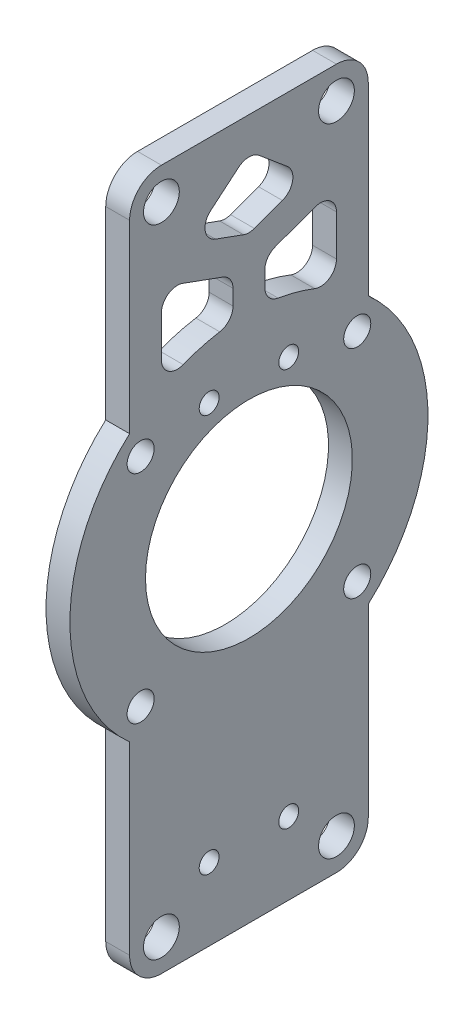
SolidWorks part; units mm, degrees
material "Сплав 2024"
ref_plane "Спереди" through (0, 0, 0) normal (0, 0, 1) x (1, 0, 0)
ref_plane "Сверху" through (0, 0, 0) normal (0, 1, 0) x (1, 0, 0)
ref_plane "Справа" through (0, 0, 0) normal (1, 0, 0) x (0, 0, -1)
sketch "Эскиз1" plane through (0, 0, 0) normal (0, 1, 0) x (1, 0, 0)
  line L1 (0, 0) -> (3, 0)
  line L2 (0, 0) -> (0, -30)
  line L3 (0, -30) -> (3, -30)
  line L4 (3, 0) -> (3, -30)
  dimension "D1" = 3
  dimension "D2" = 30
extrude "Бобышка-Вытянуть1" add sketch "Эскиз1" along normal blind 88
sketch "Эскиз2" plane through (0, 0, 0) normal (-1, 0, 0) x (0, 0, 1)
  line L0 (30, 44) -> (0, 44) construction
  line L1 (30, 88) -> (30, 0) construction
  line L2 (0, 88) -> (0, 0) construction
  line L3 (15, 88) -> (15, 0) construction
  line L4 (0, 88) -> (30, 88) construction
  line L5 (0, 0) -> (30, 0) construction
  circle A0 centre (15, 44) radius 22.5
  dimension "D1" = 45
extrude "Бобышка-Вытянуть2" add sketch "Эскиз2" against normal up to surface (3 mm away) up to face at (3, 44, 15)
sketch "Эскиз3" plane through (0, 0, 0) normal (-1, 0, 0) x (0, 0, 1)
  circle A0 centre (15, 44) radius 13
  dimension "D1" = 26
extrude "Вырез-Вытянуть1" cut sketch "Эскиз3" against normal through all
sketch "Эскиз4" plane through (3, 0, 0) normal (-1, 0, 0) x (0, 0, 1)
  line L0 (30.9099, 59.9099) -> (-0.9099, 28.0901) construction
  line L2 (30.9099, 28.0901) -> (-0.9099, 59.9099) construction
  line L3 (30, 44) -> (0, 44) construction
  circle A0 centre (15, 44) radius 19.25 construction
  circle A1 centre (15, 44) radius 22.5 construction
  dimension "D1" = 38.5
  dimension "D2" = 45
hole_wizard "Отверстие с зазором M31" positions "Эскиз6" profile "Эскиз5" hole size "M3" standard "Ansi Metric" end condition through all
sketch "Эскиз6" plane through (3, -25.0247, 7.2629) normal (-1, 0, 0) x (0, 0, 1)
  line L0 (23.647, 84.9346) -> (-8.1728, 53.1148) construction
  line L1 (23.647, 53.1148) -> (-8.1728, 84.9346) construction
  circle A0 centre (7.7371, 69.0247) radius 19.25 construction
  point P0 (21.3489, 82.6365)
  point P6 (-5.8747, 82.6365)
  point P10 (-5.8747, 55.4129)
  point P12 (21.3489, 55.4129)
sketch "Эскиз5" plane through (3, 57.6118, 28.6118) normal (0, 1, 0) x (0, 0, -1)
  line L0 (0, 0) -> (0, 3)
  line L1 (0, 3) -> (1.7, 3)
  line L2 (1.7, 3) -> (1.7, 0)
  line L5 (1.7, 0) -> (0, 0)
  line L11 (0, -6.35) -> (0, 107.95) construction
  dimension "Диаметр сквозного отверстия" = 3.4
  dimension "Глубина сквозного отверстия" = 3
sketch "Эскиз8" plane through (3, 0, 0) normal (1, 0, 0) x (0, 0, -1)
  line L0 (-15, 88) -> (-15, 0) construction
  line L1 (-30, 88) -> (0, 88) construction
  line L2 (-30, 0) -> (0, 0) construction
  line L3 (19.447, 44) -> (-49.447, 44) construction
  line L4 (0, 88) -> (0, 60.7705) construction
  line L5 (-26, 84) -> (-4, 84) construction
  line L6 (-26, 84) -> (-26, 4) construction
  line L7 (-26, 4) -> (-4, 4) construction
  line L8 (-4, 84) -> (-4, 4) construction
  line L9 (-26, 84) -> (-4, 4) construction
  line L10 (-26, 4) -> (-4, 84) construction
  line L11 (0, 0) -> (-30, 0) construction
  point P8 (-15, 44)
  point P9 (-15, 44)
  dimension "D1" = 4
  dimension "D2" = 4
  dimension "D3" = 80
  dimension "D4" = 22
hole_wizard "Отверстие с зазором M41" positions "Эскиз10" profile "Эскиз9" hole size "M4" standard "Ansi Metric" end condition through all
sketch "Эскиз10" plane through (3, 0, 0) normal (1, 0, 0) x (0, 0, -1)
  point P0 (-26, 84)
  point P3 (-4, 84)
  point P6 (-4, 4)
  point P9 (-26, 4)
sketch "Эскиз9" plane through (3, 84, 26) normal (0, 1, 0) x (0, 0, -1)
  line L0 (0, 0) -> (0, 3)
  line L1 (0, 3) -> (2.25, 3)
  line L2 (2.25, 3) -> (2.25, 0)
  line L5 (2.25, 0) -> (0, 0)
  line L11 (0, -6.35) -> (0, 107.95) construction
  dimension "Диаметр сквозного отверстия" = 4.5
  dimension "Глубина сквозного отверстия" = 3
fillet "Скругление1" radius 4 4 edges at (1.5, 0, 0) (1.5, 0, 30) (1.5, 88, 30) (1.5, 88, 0)
sketch "Эскиз11" plane through (0, 0, 0) normal (1, 0, 0) x (0, 0, -1)
  line L0 (-30, 59.12) -> (0, 59.12) construction
  line L1 (-4, 0) -> (-26, 0) construction
  line L2 (0, 84) -> (0, 60.7705) construction
  line L3 (-20, 76) -> (-20, 0) construction
  line L5 (-10, 76) -> (-10, 0) construction
  line L6 (-35.3867, 9.12) -> (5.0681, 9.12) construction
  point P8 (-10, 59.12)
  point P17 (-20, 59.12)
  point P18 (-20, 9.12)
  point P19 (-10, 9.12)
  dimension "D1" = 9.12
  dimension "D2" = 10
  dimension "D3" = 10
  dimension "D4" = 50
hole_wizard "Отверстие обработанное метчиком M3x0.51" positions "Эскиз13" profile "Эскиз12" tap size "M3x0.5" standard "Ansi Metric" end condition up to next
sketch "Эскиз13" plane through (0, 0, 0) normal (-1, 0, 0) x (0, 0, 1)
  point P0 (10, 59.12)
  point P3 (20, 59.12)
  point P6 (10, 9.12)
  point P9 (20, 9.12)
sketch "Эскиз12" plane through (0, 59.12, 10) normal (0, 1, 0) x (0, 0, 1)
  line L0 (0, 0) -> (0, 3)
  line L1 (0, 3) -> (1.25, 3)
  line L2 (1.25, 3) -> (1.25, 0)
  line L5 (1.25, 0) -> (0, 0)
  line L11 (0, -6.35) -> (0, 107.95) construction
  dimension "Диаметр проходного сверла" = 2.5
  dimension "Глубина проходного сверла" = 3
cosmetic thread "Отверстие резьбы1" parameters "D2"=3
cosmetic thread "Отверстие резьбы2" parameters "D2"=3
cosmetic thread "Отверстие резьбы3" parameters "D2"=3
cosmetic thread "Отверстие резьбы4" parameters "D2"=3
sketch "Эскиз14" plane through (0, 0, 0) normal (-1, 0, 0) x (0, 0, 1)
  line L0 (4, 88) -> (4, 0) construction
  line L1 (4, 88) -> (26, 88) construction
  line L2 (4, 0) -> (26, 0) construction
  line L3 (26, 0) -> (26, 88) construction
  line L4 (0, 84) -> (0, 60.7705) construction
  line L5 (30, 84) -> (30, 60.7705) construction
  line L6 (0, 84) -> (30, 84) construction
  line L7 (13, 71.4942) -> (13, 66.4109)
  line L8 (17, 71.4942) -> (17, 66.4109)
  line L9 (15, 88) -> (15, 0) construction
  line L10 (17, 71.4942) -> (26, 74.7699)
  line L11 (26, 74.7699) -> (26, 63.6278)
  line L12 (13, 71.4942) -> (4, 74.7699)
  line L13 (4, 74.7699) -> (4, 63.6278)
  line L14 (7.5382, 77.7388) -> (15, 75.0229)
  line L15 (22.4618, 77.7388) -> (15, 75.0229)
  line L16 (4, 74.7699) -> (15, 84) construction
  line L17 (15, 84) -> (26, 74.7699) construction
  line L18 (7.5382, 77.7388) -> (15, 84)
  line L19 (15, 84) -> (22.4618, 77.7388)
  line L20 (0, 74.7699) -> (30, 74.7699) construction
  line L21 (4, 71.4942) -> (26, 71.4942) construction
  circle A0 centre (15, 44) radius 22.5 construction
  arc A1 (4, 63.6278) -> (13, 66.4109) centre (15, 44) cw
  arc A2 (17, 66.4109) -> (26, 63.6278) centre (15, 44) cw
  point P14 (4, 63.6278)
  point P15 (26, 63.6278)
  point P33 (15, 84)
  dimension "D4" = 4
  dimension "D1" = 4
  dimension "D2" = 4
  dimension "D3" = 4
  dimension "D5" = 2
  dimension "D6" = 110
  dimension "D7" = 110
  dimension "D8" = 100
  dimension "D9" = 4
extrude "Вырез-Вытянуть2" cut sketch "Эскиз14" against normal through all
fillet "Скругление2" radius 2 12 edges at (1.5, 63.6278, 26) (1.5, 66.4109, 17) (1.5, 63.6278, 4) (1.5, 66.4109, 13) (1.5, 71.4942, 17) (1.5, 74.7699, 4) (1.5, 77.7388, 7.5382) (1.5, 77.7388, 22.4618) (1.5, 75.0229, 15) (1.5, 71.4942, 13) (1.5, 74.7699, 26) (1.5, 84, 15)
